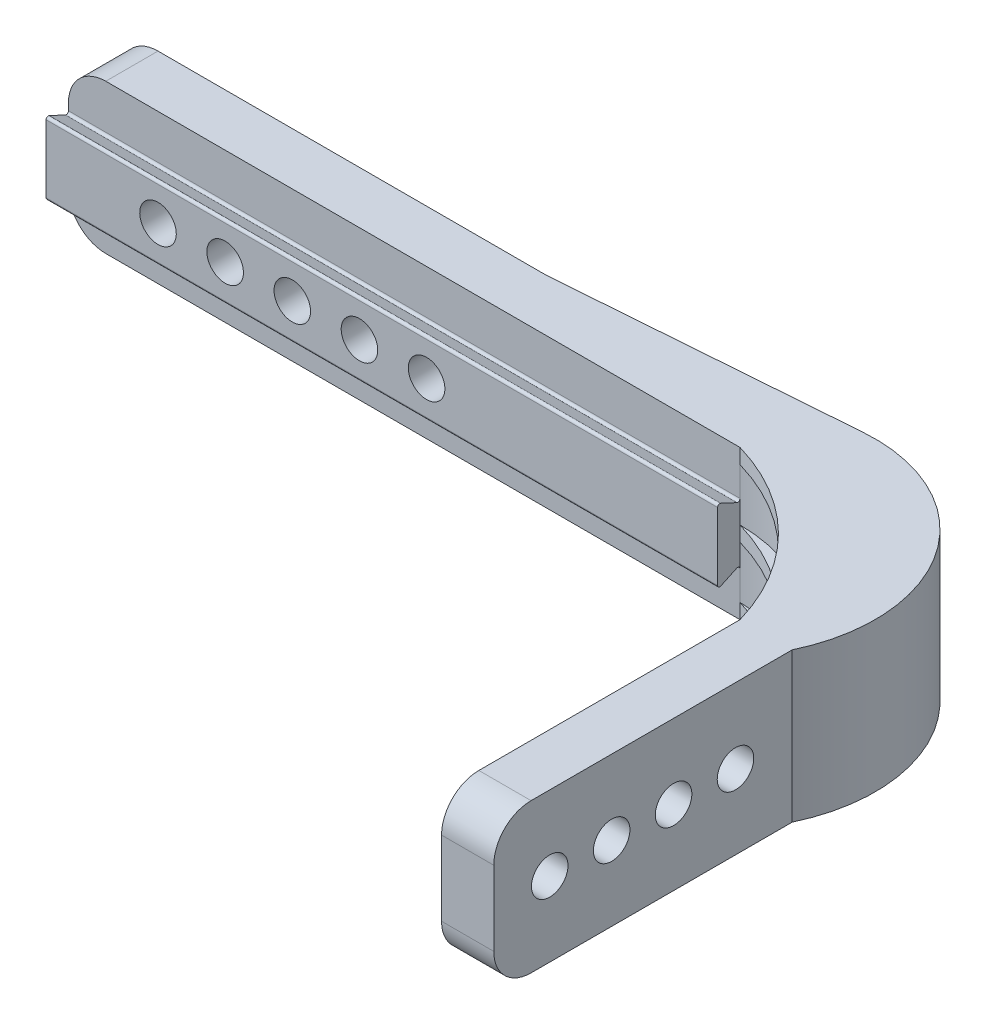
SolidWorks part; units mm, degrees
ref_plane "Front Plane" through (0, 0, 0) normal (0, 0, 1) x (1, 0, 0)
ref_plane "Top Plane" through (0, 0, 0) normal (0, 1, 0) x (1, 0, 0)
ref_plane "Right Plane" through (0, 0, 0) normal (1, 0, 0) x (0, 0, -1)
sketch "Sketch1" plane through (0, 0, 0) normal (0, 1, 0) x (1, 0, 0)
  line L0 (0, 0) -> (90, 0)
  line L1 (117, -27) -> (117, -67)
  line L2 (0, -7) -> (90, -7)
  line L3 (110, -27) -> (110, -67)
  line L4 (110, -67) -> (117, -67)
  line L5 (0, -7) -> (0, 0)
  arc A0 (90, 0) -> (117, -27) centre (90, -27) cw
  arc A1 (90, -7) -> (110, -27) centre (90, -27) cw
  dimension "D4" = 20
  dimension "D2" = 90
  dimension "D3" = 40
  dimension "D1" = 7
extrude "Boss-Extrude1" add sketch "Sketch1" along normal blind 20
sketch "Sketch2" plane through (0, 0, 0) normal (1, 0, 0) x (0, 0, -1)
  line L1 (-7, 20) -> (-7, 0) construction
  line L2 (-10, 15) -> (-10, 5)
  line L3 (-10, 5) -> (-7, 6.3989)
  line L4 (-7, 6.3989) -> (-7, 13.6011)
  line L5 (-7, 10) -> (-10, 10) construction
  line L6 (-7, 13.6011) -> (-10, 15)
  line L7 (-7, 20) -> (-27, 20) construction
  line L8 (-7, 13.6011) -> (-10, 13.6011) construction
  line L9 (-7, 6.3989) -> (-10, 6.3989) construction
  dimension "D1" = 10
  dimension "D2" = 7.2022
  dimension "D3" = 3
  dimension "D4" = 25
  dimension "D9" = 10
extrude "Boss-Extrude2" add sketch "Sketch2" along normal up to vertex (90 mm away) up to point (90, 20, 7)
ref_plane "Plane1" through (0, 0, 65) normal (0, 0, 1) x (1, 0, 0)
sketch "Sketch3" plane through (0, 0, 65) normal (0, 0, 1) x (1, 0, 0)
  line L6 (117, 12) -> (117, 8)
  line L8 (117, 20) -> (117, 0) construction
  line L9 (117, 8) -> (120, 5)
  line L10 (120, 5) -> (120, 15)
  line L11 (120, 15) -> (117, 12)
  line L12 (117, 10) -> (120, 10) construction
  line L13 (110, 20) -> (117, 20) construction
  dimension "D1" = 10
  dimension "D2" = 4
  dimension "D3" = 3
  dimension "D4" = 10
extrude "Boss-Extrude3" [suppressed] add sketch "Sketch3" against normal blind 40
sketch "Sketch4" plane through (0, 0, 0) normal (1, 0, 0) x (0, 0, -1)
  line L0 (-27, 20) -> (-67, 20) construction
  line L1 (-67, 20) -> (-67, 0) construction
  circle A0 centre (-59.5, 10) radius 2.45
  dimension "D1" = 4.9
  dimension "D2" = 10
  dimension "D3" = 7.5
extrude "Cut-Extrude1" cut sketch "Sketch4" along normal through all
pattern_linear "LPattern1" count 4 spacing 8.3 along (0, 0, -1) of "Cut-Extrude1"
sketch "Sketch5" plane through (0, 0, 0) normal (0, 0, 1) x (1, 0, 0)
  line L0 (90, 20) -> (0, 20) construction
  line L1 (0, 20) -> (0, 0) construction
  circle A0 centre (15, 10) radius 2.45
  dimension "D1" = 4.9
  dimension "D2" = 10
  dimension "D3" = 15
extrude "Cut-Extrude2" cut sketch "Sketch5" along normal blind 14
pattern_linear "LPattern2" count 5 spacing 9 along (1, 0, 0) of "Cut-Extrude2"
fillet "Fillet1" [suppressed] radius 0.5
fillet "Fillet2" radius 5 4 edges at (113.5, 0, 67) (113.5, 20, 67) (0, 0, 3.5) (0, 20, 3.5)
sketch "Sketch6" plane through (0, 0, 0) normal (0, 1, 0) x (1, 0, 0)
  line L0 (90, 0) -> (5, 0) construction
  line L1 (57.068, 0) -> (96.4605, 3)
  line L2 (90, 0) -> (57.068, 0)
  line L6 (110, -27) -> (110, -62)
  line L7 (110, -62) -> (117, -62)
  line L8 (117, -62) -> (117, -27)
  line L9 (90, 0) -> (5, 0)
  line L10 (5, 0) -> (5, -7)
  line L11 (5, -7) -> (90, -7)
  arc A0 (117, -27) -> (96.4605, 3) centre (98.0552, -17.9394) ccw
  arc A3 (117, -27) -> (90, 0) centre (90, -27) ccw
  arc A8 (117, -27) -> (90, 0) centre (90, -27) ccw
  arc A9 (110, -27) -> (90, -7) centre (90, -27) ccw
  dimension "D2" = 21
  dimension "D3" = 3
  dimension "D1" = 0
extrude "Boss-Extrude4" add sketch "Sketch6" along normal up to surface (20 mm away) up to face at (81.7168, 20, 22.7832)
sketch "Sketch8" plane through (0, 0, 0) normal (0, 1, 0) x (1, 0, 0)
  arc A0 (90, -7) -> (110, -27) centre (81.8988, -35.1012) cw
  arc A1 (90, -7) -> (110, -27) centre (90, -27) cw
extrude "Boss-Extrude5" add sketch "Sketch8" along normal blind 2
pattern_linear "LPattern3" count 3 spacing 9 along (0, 1, 0) of "Boss-Extrude5"
fillet "Fillet3" radius 0.3 4 edges at (45, 6.3989, 7) (45, 5, 10) (45, 15, 10) (45, 13.6011, 7)
fillet "Fillet4" radius 20 1 edges at (57.068, 10, 0)
